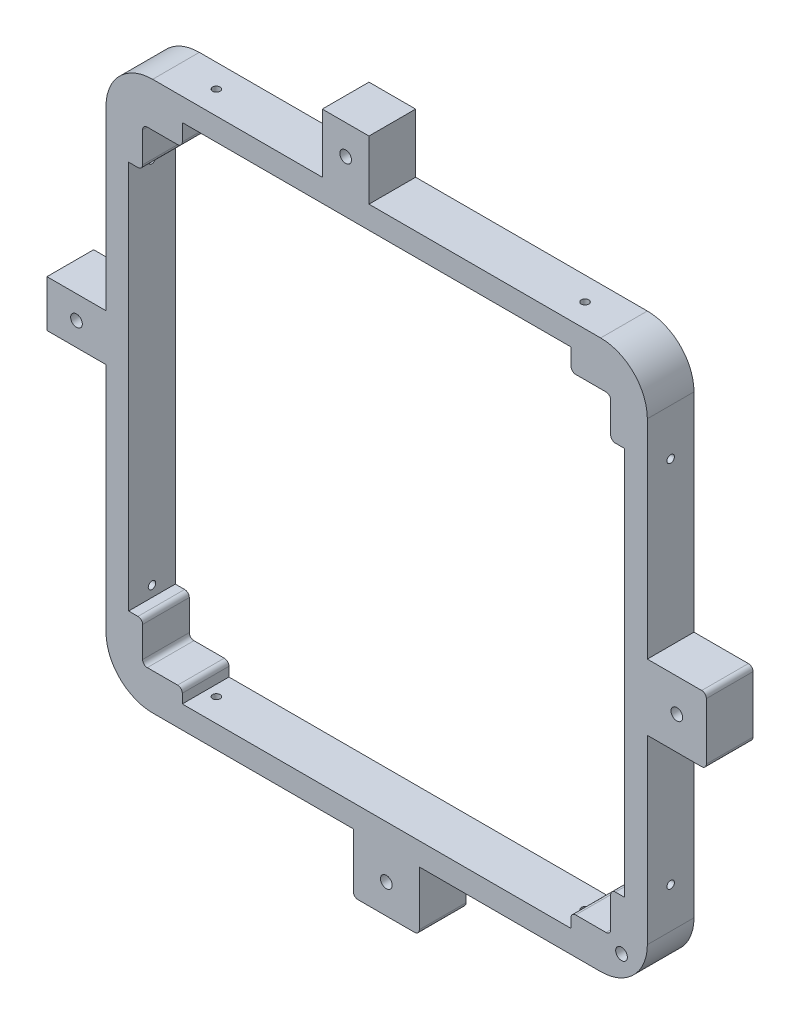
SolidWorks part; units mm, degrees
material "Nylon 101"
ref_plane "Front Plane" through (0, 0, 0) normal (0, 0, 1) x (1, 0, 0)
ref_plane "Top Plane" through (0, 0, 0) normal (0, 1, 0) x (1, 0, 0)
ref_plane "Right Plane" through (0, 0, 0) normal (1, 0, 0) x (0, 0, -1)
sketch "Sketch1" plane through (0, 0, 0) normal (0, 0, 1) x (1, 0, 0)
  line L13 (50.0019, -50.0019) -> (58, -58) construction
  line L14 (53, -41.5) -> (50.0019, -41.5)
  line L17 (41.5, -53) -> (41.5, -50.0019)
  line L18 (50.0019, -44.96) -> (53, -44.96)
  line L20 (53, -44.96) -> (53, -53)
  line L23 (53, -53) -> (44.96, -53)
  line L24 (44.96, -53) -> (44.96, -50.0019)
  line L25 (50.0019, -41.5) -> (50.0019, -50.0019)
  line L27 (50.0019, -50.0019) -> (41.5, -50.0019)
  line L35 (-41.5, 53) -> (41.5, 53)
  line L37 (50.0019, -50.0019) -> (50.0019, -41.5)
  line L38 (41.5, -50.0019) -> (50.0019, -50.0019)
  line L39 (53, -44.96) -> (50.0019, -44.96)
  line L40 (53, -53) -> (53, -44.96)
  line L42 (44.96, -53) -> (53, -53)
  line L43 (44.96, -50.0019) -> (44.96, -53)
  line L44 (53, -41.5) -> (50.0019, -41.5)
  line L45 (41.5, -53) -> (41.5, -50.0019)
  line L47 (53, -41.5) -> (53, 41.5)
  line L50 (41.5, -53) -> (-41.5, -53)
  line L52 (-41.5, -53) -> (-41.5, -50.0019)
  line L53 (-53, -41.5) -> (-50.0019, -41.5)
  line L54 (-44.96, -50.0019) -> (-44.96, -53)
  line L55 (-44.96, -53) -> (-53, -53)
  line L57 (-53, -53) -> (-53, -44.96)
  line L58 (-53, -44.96) -> (-50.0019, -44.96)
  line L59 (-41.5, -50.0019) -> (-50.0019, -50.0019)
  line L60 (-50.0019, -50.0019) -> (-50.0019, -41.5)
  line L61 (-53, -41.5) -> (-53, 41.5)
  line L63 (58, 58) -> (58, -58)
  line L65 (-50.0019, -50.0019) -> (-41.5, -50.0019)
  line L66 (-50.0019, -41.5) -> (-50.0019, -50.0019)
  line L67 (-44.96, -53) -> (-44.96, -50.0019)
  line L68 (-53, -53) -> (-44.96, -53)
  line L70 (-53, -44.96) -> (-53, -53)
  line L71 (-50.0019, -44.96) -> (-53, -44.96)
  line L72 (-41.5, -53) -> (-41.5, -50.0019)
  line L73 (-53, -41.5) -> (-50.0019, -41.5)
  line L75 (58, -58) -> (-58, -58)
  line L77 (-50.0019, -50.0019) -> (-58, -58) construction
  line L79 (-58, -58) -> (-58, 58)
  line L81 (-53, 41.5) -> (-50.0019, 41.5)
  line L82 (-41.5, 53) -> (-41.5, 50.0019)
  line L83 (-50.0019, 44.96) -> (-53, 44.96)
  line L84 (-53, 44.96) -> (-53, 53)
  line L86 (-53, 53) -> (-44.96, 53)
  line L87 (-44.96, 53) -> (-44.96, 50.0019)
  line L88 (-50.0019, 41.5) -> (-50.0019, 50.0019)
  line L89 (-50.0019, 50.0019) -> (-41.5, 50.0019)
  line L90 (-58, 58) -> (58, 58)
  line L94 (-50.0019, 50.0019) -> (-50.0019, 41.5)
  line L95 (-41.5, 50.0019) -> (-50.0019, 50.0019)
  line L96 (-53, 44.96) -> (-50.0019, 44.96)
  line L97 (-53, 53) -> (-53, 44.96)
  line L99 (-44.96, 53) -> (-53, 53)
  line L100 (-44.96, 50.0019) -> (-44.96, 53)
  line L101 (-53, 41.5) -> (-50.0019, 41.5)
  line L102 (-41.5, 53) -> (-41.5, 50.0019)
  line L106 (-50.0019, 50.0019) -> (-58, 58) construction
  line L110 (41.5, 53) -> (41.5, 50.0019)
  line L111 (53, 41.5) -> (50.0019, 41.5)
  line L112 (44.96, 50.0019) -> (44.96, 53)
  line L113 (44.96, 53) -> (53, 53)
  line L115 (53, 53) -> (53, 44.96)
  line L116 (53, 44.96) -> (50.0019, 44.96)
  line L117 (41.5, 50.0019) -> (50.0019, 50.0019)
  line L118 (50.0019, 50.0019) -> (50.0019, 41.5)
  line L123 (50.0019, 50.0019) -> (41.5, 50.0019)
  line L124 (50.0019, 41.5) -> (50.0019, 50.0019)
  line L125 (44.96, 53) -> (44.96, 50.0019)
  line L126 (53, 53) -> (44.96, 53)
  line L128 (53, 44.96) -> (53, 53)
  line L129 (50.0019, 44.96) -> (53, 44.96)
  line L130 (41.5, 53) -> (41.5, 50.0019)
  line L131 (53, 41.5) -> (50.0019, 41.5)
  line L133 (-58, 58) -> (58, 58)
  line L135 (50.0019, 50.0019) -> (58, 58) construction
  line L136 (-58, 58) -> (-58, 59.6)
  line L137 (-58, 59.6) -> (58, 59.6)
  line L138 (58, 58) -> (58, 59.6)
  line L139 (-58, 58) -> (58, 59.6) construction
  line L140 (-58, 59.6) -> (58, 58) construction
  point P2 (0, 58)
  point P4 (0, 53)
  point P6 (0, -53)
  point P7 (0, -58)
  point P10 (53, 0)
  point P11 (-53, 0)
  point P16 (-58, 0)
  point P17 (58, 0)
  point P18 (0, 58.8)
  dimension "D1" = 106
  dimension "D2" = 5
  dimension "D3" = 2.9981
  dimension "D4" = 8.04
  dimension "D5" = 11.5
  dimension "D6" = 1.6
extrude "base" add sketch "Sketch1" along normal mid plane 10 contours L20 L13 L14 L25 L18 | L13 L23 L24 L27 L17 | L13 L27 L24 L23 | L25 L13 L20 L18 | L117 L118 L116 L115 L113 L112 | L88 L89 L87 L86 L84 L83 | L59 L60 L58 L57 L55 L54 | L137 L136 L133 L79 region at (51.5009, -45.0737, 0) region at (50.1156, 47.4809, 0) region at (-45.0737, -51.5009, 0) region at (-47.4809, 50.1156, 0) region at (56.3595, 0, 0) region at (0, 58.8, 0)
ref_plane "Plane3" through (0, 0, 15) normal (0, 0, 1) x (1, 0, 0)
sketch "Sketch7" plane through (0, 0, 15) normal (0, 0, 1) x (1, 0, 0)
  line L0 (-41.65, 53.15) -> (41.65, 53.15)
  line L1 (41.65, 53.15) -> (41.65, 50.1519)
  line L2 (41.65, 50.1519) -> (50.1519, 50.1519)
  line L3 (50.1519, 50.1519) -> (50.1519, 41.65)
  line L4 (50.1519, 41.65) -> (53.15, 41.65)
  line L5 (53.15, 41.65) -> (53.15, -41.65)
  line L6 (53.15, -41.65) -> (50.1519, -41.65)
  line L7 (50.1519, -41.65) -> (50.1519, -50.1519)
  line L8 (50.1519, -50.1519) -> (41.65, -50.1519)
  line L9 (41.65, -50.1519) -> (41.65, -53.15)
  line L10 (41.65, -53.15) -> (-41.65, -53.15)
  line L11 (-41.65, -53.15) -> (-41.65, -50.1519)
  line L12 (-41.65, -50.1519) -> (-50.1519, -50.1519)
  line L13 (-50.1519, -50.1519) -> (-50.1519, -41.65)
  line L14 (-50.1519, -41.65) -> (-53.15, -41.65)
  line L15 (-53.15, -41.65) -> (-53.15, 41.65)
  line L16 (-53.15, 41.65) -> (-50.1519, 41.65)
  line L17 (-50.1519, 41.65) -> (-50.1519, 50.1519)
  line L18 (-50.1519, 50.1519) -> (-41.65, 50.1519)
  line L19 (-41.65, 50.1519) -> (-41.65, 53.15)
  line L21 (-41.5, 53) -> (41.5, 53) construction
  line L22 (-41.5, 53) -> (-41.5, 50.0019) construction
  line L23 (-50.0019, 50.0019) -> (-41.5, 50.0019) construction
  line L24 (-50.0019, 41.5) -> (-50.0019, 50.0019) construction
  line L25 (-53, 41.5) -> (-50.0019, 41.5) construction
  line L26 (-53, -41.5) -> (-53, 41.5) construction
  line L27 (-53, -41.5) -> (-50.0019, -41.5) construction
  line L28 (-50.0019, -50.0019) -> (-50.0019, -41.5) construction
  line L29 (-41.5, -50.0019) -> (-50.0019, -50.0019) construction
  line L30 (-41.5, -53) -> (-41.5, -50.0019) construction
  line L31 (41.5, -53) -> (-41.5, -53) construction
  line L32 (41.5, -53) -> (41.5, -50.0019) construction
  line L33 (50.0019, -41.5) -> (50.0019, -50.0019) construction
  line L34 (53, -41.5) -> (53, 41.5) construction
  line L35 (50.0019, 50.0019) -> (50.0019, 41.5) construction
  line L36 (53, 41.5) -> (50.0019, 41.5) construction
  line L37 (41.5, 50.0019) -> (50.0019, 50.0019) construction
  dimension "D1" = 0.15
  dimension "D2" = 0.15
  dimension "D3" = 0.15
  dimension "D4" = 0.15
  dimension "D5" = 0.15
  dimension "D6" = 0.15
  dimension "D7" = 0.15
  dimension "D8" = 0.15
  dimension "D9" = 0.15
  dimension "D10" = 0.15
  dimension "D11" = 0.15
  dimension "D12" = 0.15
  dimension "D13" = 0.15
  dimension "D14" = 0.15
  dimension "D15" = 0.15
  dimension "D16" = 0.15
  dimension "D17" = 0.15
ref_plane "arm plane" through (0, 0, 0) normal (0.7071, 0.7071, 0) x (0.7071, -0.7071, 0)
sketch "Sketch2" plane through (0, 0, 0) normal (0.7071, 0.7071, 0) x (0.7071, -0.7071, 0)
  line L4 (70.9255, 5) -> (82.0244, 5)
  line L5 (19.0244, 36) -> (8.0244, 47)
  line L6 (19.0244, 36) -> (8.0244, 36) construction
  line L8 (82.0244, 5) -> (82.0244, 47)
  line L9 (82.0244, 47) -> (8.0244, 47)
  line L13 (19.0244, 36) -> (70.9255, 36)
  line L14 (70.9255, 36) -> (70.9255, 5)
  dimension "D1" = 74
  dimension "D2" = 11
  dimension "D3" = 45
  dimension "D4" = 31
extrude "arm" add sketch "Sketch2" along normal mid plane 10
ref_plane "shim supports plane" through (0, 0, -5) normal (0, 0, -1) x (-1, 0, 0)
sketch "Sketch3" plane through (0, 0, 0) normal (0, 0, 1) x (1, 0, 0)
  line L1 (61.5355, -54.4645) -> (54.4645, -61.5355) construction
  line L6 (58, 59.6) -> (58, -50.9289) construction
  line L7 (50.9289, -58) -> (-58, -58) construction
  line L8 (9.9167, -16.9878) -> (46.6163, -53.6874) construction
  line L9 (58, -50.9289) -> (61.5355, -54.4645) construction
  line L10 (54.818, -61.8891) -> (61.8891, -54.818)
  line L11 (61.8891, -54.818) -> (58, -50.9289)
  line L12 (58, -50.9289) -> (58, -58)
  line L13 (58, -58) -> (50.9289, -58)
  line L14 (50.9289, -58) -> (54.818, -61.8891)
  dimension "D1" = 0.5
extrude "Cut-Extrude1" cut sketch "Sketch3" against normal through all
ref_plane "Plane2" through (0, 0, -5) normal (0, 0, -1) x (-1, 0, 0)
sketch "Sketch5" plane through (0, 0, -5) normal (0, 0, -1) x (-1, 0, 0)
  line L0 (-46.6163, -53.6874) -> (-43.0808, -50.1519)
  line L7 (-50.1519, -43.0808) -> (-53.6874, -46.6163)
  line L8 (-53.6874, -46.6163) -> (-53.6874, -53.6874)
  line L9 (-50.0019, -50.0019) -> (-58, -58) construction
  line L10 (-53.6874, -53.6874) -> (-46.6163, -53.6874)
  line L12 (-53.6874, -46.6163) -> (-58, -50.9289) construction
  line L14 (-50.1519, -41.65) -> (-50.1519, -50.1519) construction
  line L15 (-50.1519, -50.1519) -> (-41.65, -50.1519) construction
  line L16 (-50.1519, -43.0808) -> (-50.1519, -50.1519)
  line L17 (-50.1519, -50.1519) -> (-43.0808, -50.1519)
  dimension "D1" = 5
  dimension "D2" = 10
extrude "Boss-Extrude4" add sketch "Sketch5" along normal up to surface (31 mm away) contours L8 L10 L0 L7 | L7 L8 L10 L0 L17 L16 region at (50.1519, -53.5374, -5) up to face at (31.8021, -31.8021, -36)
extrude "clearance" cut sketch "Sketch7" against normal up to surface (20 mm away) up to face at (0, 0, -5)
sketch "Sketch42" plane through (0, 0, -5) normal (0, 0, -1) x (-1, 0, 0)
  line L5 (-41.65, 53.15) -> (-41.65, 50.1519) construction
  line L6 (-41.65, 53.15) -> (41.65, 53.15)
  line L9 (-41.65, 53.15) -> (-41.65, 54.75)
  line L14 (-41.65, 54.75) -> (41.65, 54.75)
  line L15 (41.65, 53.15) -> (41.65, 54.75)
  line L16 (-41.65, 53.15) -> (41.65, 54.75) construction
  line L17 (-41.65, 54.75) -> (41.65, 53.15) construction
  line L18 (41.65, 50.1519) -> (41.65, 53.15) construction
  line L19 (41.65, 53.15) -> (-41.65, 53.15) construction
  point P0 (0, 53.95)
  dimension "D1" = 1.6
extrude "Cut-Extrude2" cut sketch "Sketch42" against normal through all both and the other way through all
hole_wizard "M2x0.4 Tapped Hole1" positions "Sketch11" profile "Sketch12" tap size "M2x0.4" standard "ANSI Metric" end condition through all
sketch "Sketch11" plane through (0, 0, 0) normal (0, 1, 0) x (1, 0, 0)
  line L0 (58, -5) -> (58, 5) construction
  line L1 (-58, -5) -> (-58, 5) construction
  line L2 (-58, 5) -> (58, 5) construction
  point P0 (-39.35, 0)
  point P2 (39.65, 0)
  dimension "D1" = 18.35
  dimension "D2" = 18.65
  dimension "D3" = 5
sketch "Sketch12" plane through (-39.35, 0, 0) normal (1, 0, 0) x (0, 0, -1)
  line L0 (0, 0) -> (0, 59.6)
  line L1 (0, 59.6) -> (0.8, 59.6)
  line L2 (0.8, 59.6) -> (0.8, 0)
  line L5 (0.8, 0) -> (0, 0)
  line L11 (0, -6.35) -> (0, 107.95) construction
  dimension "Thru Tap Drill Dia." = 1.6
  dimension "Thru Tap Drill Depth" = 59.6
cosmetic thread "Hole Thread1" parameters "D2"=2
cosmetic thread "Hole Thread2" parameters "D2"=2
mirror "Mirror1" about plane through (0, 0, 0) normal (0, 1, 0) of "M2x0.4 Tapped Hole1"
cosmetic thread "Hole Thread3" parameters "D2"=2
cosmetic thread "Hole Thread4" parameters "D2"=2
sketch "Sketch13" plane through (0, 0, 0) normal (1, 0, 0) x (0, 0, -1)
  line L2 (5, 41.65) -> (-5, 41.65) construction
  circle A0 centre (0, 39.65) radius 0.8
  circle A1 centre (0, -39.35) radius 0.8
  dimension "D1" = 1.6
  dimension "D3" = 79
  dimension "D2" = 2
hole_wizard "M2x0.4 Tapped Hole2" positions "Sketch14" profile "Sketch15" tap size "M2x0.4" standard "ANSI Metric" end condition through all
sketch "Sketch14" plane through (0, 0, 0) normal (1, 0, 0) x (0, 0, -1)
  point P0 (0, 39.65)
  point P3 (0, -39.35)
sketch "Sketch15" plane through (0, 39.65, 0) normal (0, 1, 0) x (0, 0, 1)
  line L0 (0, 0) -> (0, 58)
  line L1 (0, 58) -> (0.8, 58)
  line L2 (0.8, 58) -> (0.8, 0)
  line L5 (0.8, 0) -> (0, 0)
  line L11 (0, -6.35) -> (0, 107.95) construction
  dimension "Thru Tap Drill Dia." = 1.6
  dimension "Thru Tap Drill Depth" = 58
cosmetic thread "Hole Thread5" parameters "D2"=2
cosmetic thread "Hole Thread6" parameters "D2"=2
mirror "Mirror2" about plane through (0, 0, 0) normal (1, 0, 0) of "M2x0.4 Tapped Hole2"
cosmetic thread "Hole Thread7" parameters "D2"=2
cosmetic thread "Hole Thread8" parameters "D2"=2
sketch "Sketch16" plane through (0, 0, -5) normal (0, 0, -1) x (-1, 0, 0)
  line L0 (53.15, 11.65) -> (70.65, 11.65)
  line L6 (53.15, -41.65) -> (53.15, 41.65) construction
  line L9 (53.15, 41.65) -> (50.1519, 41.65) construction
  line L10 (-58, -58) -> (58, 59.6) construction
  line L19 (53.15, 1.65) -> (53.15, 11.65)
  line L20 (53.15, 1.65) -> (70.65, 1.65)
  line L21 (70.65, 1.65) -> (70.65, 11.65)
  dimension "D1" = 10
  dimension "D2" = 17.5
  dimension "D3" = 30
extrude "extender" add sketch "Sketch16" along normal blind 28.6716 contours L19 region at (-61.9, 6.65, -5)
ref_plane "Plane5" through (0, 0, -33.6716) normal (0, 0, -1) x (-1, 0, 0)
sketch "Sketch17" plane through (0, 0, -33.6716) normal (0, 0, -1) x (-1, 0, 0)
  line L2 (194.5714, 153.0714) -> (208.3214, 139.3214)
  line L4 (53.15, 1.65) -> (53.15, 11.65)
  line L5 (53.15, 11.65) -> (194.5714, 153.0714)
  line L9 (-50.9289, -58) -> (-2.1386, -9.2096) construction
  line L14 (208.3214, 139.3214) -> (70.65, 1.65)
  line L15 (70.65, 1.65) -> (53.15, 1.65)
  dimension "D2" = 200
extrude "angled horizontal" add sketch "Sketch17" along normal up to surface (13.3284 mm away) up to face at (35.6554, -35.6554, -47)
sketch "Sketch21" plane through (0, 0, 0) normal (0, 0, 1) x (1, 0, 0)
  line L0 (-53.15, 1.65) -> (-53.15, 11.65)
  line L1 (-70.65, 11.65) -> (-53.15, 11.65)
  line L6 (-11.65, 54.75) -> (-1.65, 54.75)
  line L7 (-70.65, 11.65) -> (-70.65, 1.65)
  line L12 (-53.15, 38.85) -> (-53.15, 40.45) construction
  line L13 (-70.65, 1.65) -> (-53.15, 1.65)
  line L14 (-53.15, 11.65) -> (-53.15, 1.65) construction
  line L15 (-58, 1.65) -> (-70.65, 1.65) construction
  line L19 (-1.65, 54.75) -> (-1.65, 72.25)
  line L20 (-1.65, 72.25) -> (-11.65, 72.25)
  line L21 (-11.65, 72.25) -> (-11.65, 54.75)
  line L22 (41.65, 54.75) -> (-41.65, 54.75) construction
  line L24 (-41.65, 50.1519) -> (-41.65, 54.75) construction
  dimension "D1" = 30
extrude "Arm Holder" add sketch "Sketch21" along normal up to surface (5 mm away) and the other way up to surface (5 mm away) up to face at (0, 0.16, 5) other way up to face at (-64.325, 6.65, -5)
sketch "Sketch44" plane through (0, 0, -5) normal (0, 0, -1) x (-1, 0, 0)
  line L0 (-41.65, 54.75) -> (41.65, 54.75) construction
  line L1 (11.65, 72.25) -> (1.65, 72.25)
  line L2 (11.65, 72.25) -> (11.65, 54.75)
  line L3 (11.65, 54.75) -> (1.65, 54.75)
  line L4 (1.65, 72.25) -> (1.65, 54.75)
  line L5 (11.65, 72.25) -> (1.65, 54.75) construction
  line L6 (11.65, 54.75) -> (1.65, 72.25) construction
  line L7 (11.65, 72.25) -> (11.65, 59.6) construction
  line L8 (1.65, 59.6) -> (1.65, 72.25) construction
  line L9 (1.65, 72.25) -> (11.65, 72.25) construction
  point P0 (6.65, 63.5)
extrude "Boss-Extrude20" add sketch "Sketch44" along normal up to surface (28.6716 mm away) up to face at (-119.4685, 63.4685, -33.6716)
sketch "Sketch45" plane through (0, 0, -33.6716) normal (0, 0, -1) x (-1, 0, 0)
  line L0 (1.65, 72.25) -> (1.65, 54.75)
  line L1 (1.65, 54.75) -> (11.65, 54.75)
  line L2 (11.65, 54.75) -> (152.2714, 195.3714)
  line L3 (152.2714, 195.3714) -> (138.5214, 209.1214)
  line L4 (138.5214, 209.1214) -> (1.65, 72.25)
  line L5 (194.5714, 153.0714) -> (53.15, 11.65) construction
  line L6 (208.3214, 139.3214) -> (194.5714, 153.0714) construction
extrude "Boss-Extrude21" add sketch "Sketch45" along normal up to surface (13.3284 mm away) up to face at (-115.9685, 61.4685, -47)
sketch "Sketch46" plane through (-34.5, -34.5, 0) normal (-0.7071, -0.7071, 0) x (0, 0, 1)
  line L8 (-47, 232.4921) -> (-47, 245.8205)
  line L9 (-47, 245.8205) -> (-33.6716, 245.8205)
  line L11 (-33.6716, 245.8205) -> (-47, 232.4921)
  line L12 (-47, 51.1238) -> (-47, 245.8205) construction
  line L13 (-33.6716, 51.1238) -> (-33.6716, 245.8205) construction
  dimension "D1" = 45
extrude "Boss-Extrude22" add sketch "Sketch46" against normal up to surface (79.2667 mm away) up to face at (-81.9607, 125.0607, -40.3358)
fillet "Fillet1" radius 1 12 edges at (50.1519, -41.65, 0) (41.65, -50.1519, 0) (-50.1519, -41.65, 0) (-41.65, -50.1519, 0) (-50.1519, 41.65, 0) (-41.65, 50.1519, 0) (41.65, 50.1519, 0) (50.1519, 41.65, 0) (50.1519, 50.1519, 0) (50.1519, -50.1519, -15.5) (-50.1519, -50.1519, 0) (-50.1519, 50.1519, 0)
fillet "Fillet2" radius 10 4 edges at (58, -58, -21) (-58, -58, 0) (-58, 59.6, 0) (58, 59.6, 0)
hole_wizard "M3x0.5 Tapped Hole2" positions "Sketch28" profile "Sketch29" tap size "M3x0.5" standard "ANSI Metric" end condition through all
sketch "Sketch28" plane through (0, 0, -47) normal (0, 0, -1) x (-1, 0, 0)
  line L1 (-57.6593, -50.5882) -> (-9.2096, -2.1386) construction
  arc A0 (-57.6593, -50.5882) -> (-50.5882, -57.6593) centre (-48, -48) ccw construction
  point P0 (-52.4654, -52.4654)
  point P11 (-55.0711, -55.0711)
  dimension "D1" = 5
  dimension "D2" = 3.685
cosmetic thread "Hole Thread13" parameters "D2"=3
sketch "Sketch29" plane through (52.4654, -52.4654, -47) normal (1, 0, 0) x (0, 1, 0)
  line L0 (0, 0) -> (0, 52)
  line L1 (0, 52) -> (1.25, 52)
  line L2 (1.25, 52) -> (1.25, 0)
  line L5 (1.25, 0) -> (0, 0)
  line L11 (0, -6.35) -> (0, 107.95) construction
  dimension "Thru Tap Drill Dia." = 2.5
  dimension "Thru Tap Drill Depth" = 52
hole_wizard "M3x0.5 Tapped Hole3" positions "Sketch36" profile "Sketch38" tap size "M3x0.5" standard "ANSI Metric"
sketch "Sketch36" plane through (0, 0, 5) normal (0, 0, 1) x (1, 0, 0)
  line L1 (-53.15, 11.65) -> (-53.15, 1.65) construction
  line L2 (-64.325, 11.65) -> (-64.325, 6.65) construction
  line L3 (-58, 11.65) -> (-70.65, 11.65) construction
  line L4 (-64.325, 6.65) -> (-70.65, 6.65) construction
  line L5 (-70.65, 11.65) -> (-70.65, 1.65) construction
  line L6 (-1.65, 65.925) -> (-6.65, 65.925) construction
  line L7 (-1.65, 59.6) -> (-1.65, 72.25) construction
  line L8 (-6.65, 65.925) -> (-6.65, 72.25) construction
  line L9 (-1.65, 72.25) -> (-11.65, 72.25) construction
  point P0 (-64.325, 6.65)
  point P9 (-53.15, 6.65)
  point P17 (-6.65, 65.925)
sketch "Sketch38" plane through (-64.325, 6.65, 5) normal (1, 0, 0) x (0, -1, 0)
  line L0 (0, 0) -> (0, 30.5611)
  line L1 (0, 30.5611) -> (1.25, 29.81)
  line L2 (1.25, 29.81) -> (1.25, 0)
  line L5 (1.25, 0) -> (0, 0)
  line L10 (0, 30.5611) -> (-1.25, 29.81) construction
  line L11 (0, -6.35) -> (0, 107.95) construction
  dimension "Tap Drill Dia." = 2.5
  dimension "Tap Drill Depth" = 29.81
  dimension "Drill Angle" = 118
cosmetic thread "Hole Thread14" parameters "D1"=10, "D2"=3
cosmetic thread "Hole Thread15" parameters "D1"=10, "D2"=3
fillet "Fillet3" radius 1 2 edges at (-53.15, 1.65, -26) (-1.65, 54.75, -26)
sketch "Sketch47" plane through (-3.5355, -3.5355, 0) normal (-0.7071, -0.7071, 0) x (0, 0, 1)
  line L0 (-47, -76.5425) -> (-47, -8.0244) construction
  line L1 (-47, -37.4749) -> (-36, -37.4749)
  line L2 (-47, -37.4749) -> (-47, -47.4749)
  line L3 (-47, -47.4749) -> (-36, -47.4749)
  line L4 (-36, -37.4749) -> (-36, -47.4749)
  line L5 (-47, -37.4749) -> (-36, -47.4749) construction
  line L6 (-47, -47.4749) -> (-36, -37.4749) construction
  line L7 (-36, -19.0244) -> (-36, -65.9255) construction
  point P0 (-41.5, -42.4749)
  point P10 (-36, -42.4749)
  dimension "D1" = 10
extrude "Boss-Extrude23" add sketch "Sketch47" along normal up to surface (39.5495 mm away) up to face at (-39.35, -58, 0.8)
sketch "Sketch48" plane through (0, 0, -5) normal (0, 0, -1) x (-1, 0, 0)
  line L0 (-9.1397, -58) -> (-13.9897, -53.15)
  line L5 (-48, -58) -> (48, -58) construction
  line L6 (-41.65, -53.15) -> (41.65, -53.15) construction
  line L7 (-13.9897, -53.15) -> (0.1524, -53.15)
  line L10 (0.1524, -53.15) -> (5.0024, -58)
  line L11 (5.0024, -58) -> (-9.1397, -58)
  line L12 (-9.1397, -58) -> (-30.0343, -37.1054) construction
  line L13 (5.0024, -58) -> (-22.9632, -30.0343) construction
  line L15 (-9.1397, -58) -> (5.0024, -58)
  line L16 (-9.1397, -58) -> (-9.1397, -70.65)
  line L17 (-9.1397, -70.65) -> (5.0024, -70.65)
  line L18 (5.0024, -58) -> (5.0024, -70.65)
  line L19 (-9.1397, -58) -> (5.0024, -70.65) construction
  line L20 (-9.1397, -70.65) -> (5.0024, -58) construction
  point P12 (-2.0686, -64.325)
  line M17 (-48, -58) -> (48, -58)
  line M30 (41.65, -53.15) -> (-41.65, -53.15)
  dimension "D1" = 12.65
extrude "Boss-Extrude24" add sketch "Sketch48" along normal up to surface (31 mm away) contours L10 L0 M30 M17 region at (4.4936, -55.575, -5) up to face at (27.6783, -40.2788, -36)
extrude "Boss-Extrude25" add sketch "Sketch48<3>" along normal up to surface (42 mm away) contours L18 L16 L17 M17 region at (2.0686, -64.325, -5) up to face at (52.4654, -51.2154, -47)
sketch "Sketch48<3>" plane through (0, 0, -5) normal (0, 0, -1) x (-1, 0, 0) same geometry as "Sketch48"
extrude "Boss-Extrude26" add sketch "Sketch48<4>" against normal up to surface (10 mm away) contours L18 L16 L17 M17 region at (2.0686, -64.325, -5) up to face at (-63.075, 6.65, 5)
sketch "Sketch48<4>" plane through (0, 0, -5) normal (0, 0, -1) x (-1, 0, 0) same geometry as "Sketch48"
hole_wizard "M3x0.5 Tapped Hole4" positions "Sketch49" profile "Sketch50" tap size "M3x0.5" standard "ANSI Metric"
sketch "Sketch49" plane through (0, 0, 5) normal (0, 0, 1) x (1, 0, 0)
  line L0 (2.0686, -64.325) -> (9.1397, -64.325) construction
  line L1 (9.1397, -58) -> (9.1397, -70.65) construction
  line L3 (2.0686, -64.325) -> (2.0686, -70.65) construction
  line L4 (9.1397, -70.65) -> (-5.0024, -70.65) construction
  point P0 (2.0686, -64.325)
sketch "Sketch50" plane through (2.0686, -64.325, 5) normal (1, 0, 0) x (0, -1, 0)
  line L0 (0, 0) -> (0, 30.5611)
  line L1 (0, 30.5611) -> (1.25, 29.81)
  line L2 (1.25, 29.81) -> (1.25, 0)
  line L5 (1.25, 0) -> (0, 0)
  line L10 (0, 30.5611) -> (-1.25, 29.81) construction
  line L11 (0, -6.35) -> (0, 107.95) construction
  dimension "Tap Drill Dia." = 2.5
  dimension "Tap Drill Depth" = 29.81
  dimension "Drill Angle" = 118
cosmetic thread "Hole Thread16" parameters "D1"=28.31, "D2"=3
mirror "Mirror3" about plane through (0, 0, 0) normal (0.7071, 0.7071, 0) of "M3x0.5 Tapped Hole4", "Boss-Extrude26", "Boss-Extrude24", "Boss-Extrude25", "Boss-Extrude23"
cosmetic thread "Hole Thread17" parameters "D1"=28.31, "D2"=3
fillet "Fillet6" radius 1 6 edges at (70.65, -2.0686, -47) (2.0686, -70.65, -47) (-5.0024, -70.65, -21) (9.1397, -70.65, -21) (70.65, -9.1397, -21) (70.65, 5.0024, -21)
hole_wizard "M3x0.5 Tapped Hole5" positions "Sketch51" profile "Sketch52" tap size "M3x0.5" standard "ANSI Metric"
sketch "Sketch51" plane through (0, 0, -47) normal (0, 0, -1) x (-1, 0, 0)
  line L0 (53.15, 7.15) -> (62.4, 7.15) construction
  line L1 (62.4, 7.15) -> (62.4, 1.65) construction
  line L3 (53.15, 11.65) -> (53.15, 2.65) construction
  line L4 (54.15, 1.65) -> (70.65, 1.65) construction
  line L5 (7.15, 54.75) -> (7.15, 64) construction
  line L6 (7.15, 64) -> (1.65, 64) construction
  line L8 (1.65, 55.75) -> (1.65, 72.25) construction
  line L9 (11.65, 54.75) -> (2.65, 54.75) construction
  line L10 (-63.825, -2.0686) -> (-63.825, 5.0024) construction
  line L11 (-69.65, 5.0024) -> (-58, 5.0024) construction
  line L13 (-63.825, -2.0686) -> (-69.65, -2.0686) construction
  line L14 (-69.65, 5.0024) -> (-69.65, -9.1397) construction
  line L16 (-2.0686, -63.825) -> (-2.0686, -69.65) construction
  line L17 (-9.1397, -69.65) -> (5.0024, -69.65) construction
  line L19 (-2.0686, -63.825) -> (5.0024, -63.825) construction
  line L20 (5.0024, -69.65) -> (5.0024, -58) construction
  point P0 (-2.0686, -63.825)
  point P2 (-63.825, -2.0686)
  point P4 (62.4, 7.15)
  point P6 (7.15, 64)
  point P60 (0, 0)
  point P61 (0, 0)
sketch "Sketch52" plane through (2.0686, -63.825, -47) normal (1, 0, 0) x (0, 1, 0)
  line L0 (0, 0) -> (0, 30.5611)
  line L1 (0, 30.5611) -> (1.25, 29.81)
  line L2 (1.25, 29.81) -> (1.25, 0)
  line L5 (1.25, 0) -> (0, 0)
  line L10 (0, 30.5611) -> (-1.25, 29.81) construction
  line L11 (0, -6.35) -> (0, 107.95) construction
  dimension "Tap Drill Dia." = 2.5
  dimension "Tap Drill Depth" = 29.81
  dimension "Drill Angle" = 118
cosmetic thread "Hole Thread18" parameters "D1"=28.31, "D2"=3
cosmetic thread "Hole Thread19" parameters "D1"=28.31, "D2"=3
cosmetic thread "Hole Thread20" parameters "D1"=28.31, "D2"=3
cosmetic thread "Hole Thread21" parameters "D1"=28.31, "D2"=3
split "Split1" bodies to split 158 146 resulting bodies 142 split by face at (-43.8546, -39.5319, -5)
